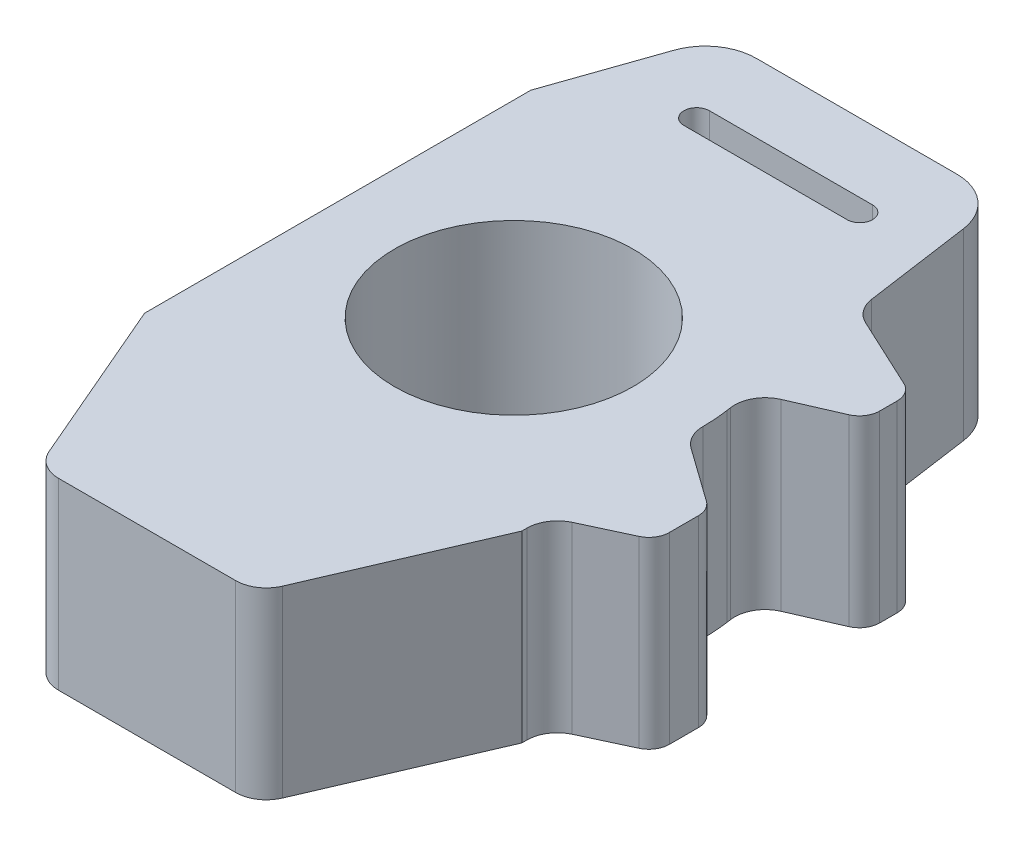
SolidWorks part; units mm, degrees
ref_plane "Front Plane" through (0, 0, 0) normal (0, 0, 1) x (1, 0, 0)
ref_plane "Top Plane" through (0, 0, 0) normal (0, 1, 0) x (1, 0, 0)
ref_plane "Right Plane" through (0, 0, 0) normal (1, 0, 0) x (0, 0, -1)
sketch "Sketch1" plane through (0, 0, 0) normal (0, 1, 0) x (1, 0, 0)
  line L0 (-55.5625, -55.5625) -> (-33.4015, -107.1225) construction
  line L1 (-55.5625, 63.5) -> (-55.5625, -55.5625) construction
  line L2 (-44.2417, 96.0375) -> (-55.5625, 63.5) construction
  line L3 (-32.247, 104.5642) -> (30.2506, 104.5642) construction
  line L4 (47.5603, 60.2912) -> (42.8246, 93.6493) construction
  line L5 (54.767, 50.5662) -> (77.0794, 40.1617) construction
  line L6 (78.9125, 37.2842) -> (78.9125, 31.8598) construction
  line L7 (77.0083, 28.9502) -> (62.3171, 22.5338) construction
  line L8 (55.0109, 7.8097) -> (54.8263, 9.1103) construction
  line L9 (60.8833, -10.1158) -> (77.5822, -22.0366) construction
  line L10 (78.9125, -24.6207) -> (78.9125, -33.6635) construction
  line L11 (77.0794, -36.5411) -> (62.8952, -43.1552) construction
  line L12 (55.5625, -55.5625) -> (55.5625, -54.6653) construction
  line L13 (33.4015, -107.1225) -> (55.5625, -55.5625) construction
  line L14 (-27.5676, -110.965) -> (27.5676, -110.965) construction
  line L15 (-55.5625, -55.5625) -> (-33.4015, -107.1225) construction
  line L16 (-55.5625, 63.5) -> (-55.5625, -55.5625) construction
  line L17 (-44.2417, 96.0375) -> (-55.5625, 63.5) construction
  line L18 (-32.247, 104.5642) -> (30.2506, 104.5642) construction
  line L19 (47.5603, 60.2912) -> (42.8246, 93.6493) construction
  line L20 (54.767, 50.5662) -> (77.0794, 40.1617) construction
  line L21 (78.9125, 37.2842) -> (78.9125, 31.8598) construction
  line L22 (77.0083, 28.9502) -> (62.3171, 22.5338) construction
  line L23 (55.0109, 7.8097) -> (54.8263, 9.1103) construction
  line L24 (60.8833, -10.1158) -> (77.5822, -22.0366) construction
  line L25 (78.9125, -24.6207) -> (78.9125, -33.6635) construction
  line L26 (77.0794, -36.5411) -> (62.8952, -43.1552) construction
  line L27 (55.5625, -55.5625) -> (55.5625, -54.6653) construction
  line L28 (33.4015, -107.1225) -> (55.5625, -55.5625) construction
  line L29 (-27.5676, -110.965) -> (27.5676, -110.965) construction
  line L30 (-58.7375, -56.2159) -> (-36.3185, -108.3762)
  line L31 (-27.5676, -114.14) -> (27.5676, -114.14)
  line L32 (36.3185, -108.3762) -> (58.7375, -56.2159)
  line L33 (58.7375, -56.2159) -> (58.7375, -54.6653)
  line L34 (78.4212, -39.4186) -> (64.2371, -46.0327)
  line L35 (82.0875, -24.6207) -> (82.0875, -33.6635)
  line L36 (62.728, -7.5317) -> (79.427, -19.4525)
  line L37 (58.1544, 8.256) -> (57.9697, 9.5566)
  line L38 (78.2791, 26.0406) -> (63.5878, 19.6242)
  line L39 (82.0875, 37.2842) -> (82.0875, 31.8598)
  line L40 (56.1088, 53.4437) -> (78.4212, 43.0393)
  line L41 (50.7038, 60.7375) -> (45.968, 94.0955)
  line L42 (-32.247, 107.7392) -> (30.2506, 107.7392)
  line L43 (-47.2404, 97.0808) -> (-58.7375, 64.0366)
  line L44 (-58.7375, 64.0366) -> (-58.7375, -56.2159)
  arc A0 (-33.4015, -107.1225) -> (-27.5676, -110.965) centre (-27.5676, -104.615) ccw construction
  arc A1 (-32.247, 104.5642) -> (-44.2417, 96.0375) centre (-32.247, 91.8642) ccw construction
  arc A2 (42.8246, 93.6493) -> (30.2506, 104.5642) centre (30.2506, 91.8642) ccw construction
  arc A3 (47.5603, 60.2912) -> (54.767, 50.5662) centre (60.1342, 62.0763) ccw construction
  arc A4 (78.9125, 37.2842) -> (77.0794, 40.1617) centre (75.7375, 37.2842) ccw construction
  arc A5 (77.0083, 28.9502) -> (78.9125, 31.8598) centre (75.7375, 31.8598) ccw construction
  arc A6 (62.3171, 22.5338) -> (54.8263, 9.1103) centre (67.4002, 10.8954) ccw construction
  arc A7 (55.5622, 0.1796) -> (55.0109, 7.8097) centre (0, 0) ccw construction
  arc A8 (55.5622, 0.1796) -> (60.8833, -10.1158) centre (68.2621, 0.2207) ccw construction
  arc A9 (78.9125, -24.6207) -> (77.5822, -22.0366) centre (75.7375, -24.6207) ccw construction
  arc A10 (77.0794, -36.5411) -> (78.9125, -33.6635) centre (75.7375, -33.6635) ccw construction
  arc A11 (62.8952, -43.1552) -> (55.5625, -54.6653) centre (68.2625, -54.6653) ccw construction
  arc A12 (27.5676, -110.965) -> (33.4015, -107.1225) centre (27.5676, -104.615) ccw construction
  arc A13 (-33.4015, -107.1225) -> (-27.5676, -110.965) centre (-27.5676, -104.615) ccw construction
  arc A14 (-32.247, 104.5642) -> (-44.2417, 96.0375) centre (-32.247, 91.8642) ccw construction
  arc A15 (42.8246, 93.6493) -> (30.2506, 104.5642) centre (30.2506, 91.8642) ccw construction
  arc A16 (47.5603, 60.2912) -> (54.767, 50.5662) centre (60.1342, 62.0763) ccw construction
  arc A17 (78.9125, 37.2842) -> (77.0794, 40.1617) centre (75.7375, 37.2842) ccw construction
  arc A18 (77.0083, 28.9502) -> (78.9125, 31.8598) centre (75.7375, 31.8598) ccw construction
  arc A19 (62.3171, 22.5338) -> (54.8263, 9.1103) centre (67.4002, 10.8954) ccw construction
  arc A20 (55.5622, 0.1796) -> (55.0109, 7.8097) centre (0, 0) ccw construction
  arc A21 (55.5622, 0.1796) -> (60.8833, -10.1158) centre (68.2621, 0.2207) ccw construction
  arc A22 (78.9125, -24.6207) -> (77.5822, -22.0366) centre (75.7375, -24.6207) ccw construction
  arc A23 (77.0794, -36.5411) -> (78.9125, -33.6635) centre (75.7375, -33.6635) ccw construction
  arc A24 (62.8952, -43.1552) -> (55.5625, -54.6653) centre (68.2625, -54.6653) ccw construction
  arc A25 (27.5676, -110.965) -> (33.4015, -107.1225) centre (27.5676, -104.615) ccw construction
  arc A26 (-36.3185, -108.3762) -> (-27.5676, -114.14) centre (-27.5676, -104.615) ccw
  arc A27 (27.5676, -114.14) -> (36.3185, -108.3762) centre (27.5676, -104.615) ccw
  arc A28 (64.2371, -46.0327) -> (58.7375, -54.6653) centre (68.2625, -54.6653) ccw
  arc A29 (78.4212, -39.4186) -> (82.0875, -33.6635) centre (75.7375, -33.6635) ccw
  arc A30 (82.0875, -24.6207) -> (79.427, -19.4525) centre (75.7375, -24.6207) ccw
  arc A31 (58.7372, 0.1899) -> (62.728, -7.5317) centre (68.2621, 0.2207) ccw
  arc A32 (58.7372, 0.1899) -> (58.1544, 8.256) centre (0, 0) ccw
  arc A33 (63.5878, 19.6242) -> (57.9697, 9.5566) centre (67.4002, 10.8954) ccw
  arc A34 (78.2791, 26.0406) -> (82.0875, 31.8598) centre (75.7375, 31.8598) ccw
  arc A35 (82.0875, 37.2842) -> (78.4212, 43.0393) centre (75.7375, 37.2842) ccw
  arc A36 (50.7038, 60.7375) -> (56.1088, 53.4437) centre (60.1342, 62.0763) ccw
  arc A37 (45.968, 94.0955) -> (30.2506, 107.7392) centre (30.2506, 91.8642) ccw
  arc A38 (-32.247, 107.7392) -> (-47.2404, 97.0808) centre (-32.247, 91.8642) ccw
  dimension "D1" = 3.175
extrude "Boss-Extrude1" add sketch "Sketch1" along normal blind 28.575 and the other way blind 28.575 contours L30 A26 L31 A27 L32 L33 A28 L34 A29 L35 A30 L36 A31 A32 L37 A33 L38 A34 L39 A35 L40 A36 L41 A37 L42 A38 L43 L44
sketch "Sketch2" plane through (0, 28.575, 0) normal (0, 1, 0) x (1, 0, 0)
  circle A0 centre (0, 0) radius 37.1475
  circle A1 centre (0, 0) radius 43.4975 construction
  dimension "D1" = 6.35
extrude "Cut-Extrude1" cut sketch "Sketch2" against normal through all
sketch "Sketch5" plane through (0, -28.575, 0) normal (0, -1, 0) x (1, 0, 0)
  line L0 (-25.4, -92.6643) -> (25.4, -92.6643) construction
  line L1 (25.4, -72.0141) -> (-25.4, -72.0141) construction
  line L2 (-25.4, -92.6643) -> (25.4, -92.6643) construction
  line L3 (25.4, -72.0141) -> (-25.4, -72.0141) construction
  line L4 (-25.4, -86.3143) -> (25.4, -86.3143)
  line L5 (25.4, -78.3641) -> (-25.4, -78.3641)
  arc A0 (-25.4, -72.0141) -> (-25.4, -92.6643) centre (-25.4, -82.3392) ccw construction
  arc A1 (25.4, -92.6643) -> (25.4, -72.0141) centre (25.4, -82.3392) ccw construction
  arc A2 (-25.4, -72.0141) -> (-25.4, -92.6643) centre (-25.4, -82.3392) ccw construction
  arc A3 (25.4, -92.6643) -> (25.4, -72.0141) centre (25.4, -82.3392) ccw construction
  arc A4 (25.4, -86.3143) -> (25.4, -78.3641) centre (25.4, -82.3392) ccw
  arc A5 (-25.4, -78.3641) -> (-25.4, -86.3143) centre (-25.4, -82.3392) ccw
  dimension "D1" = 6.35
extrude "Cut-Extrude2" cut sketch "Sketch5" against normal through all
